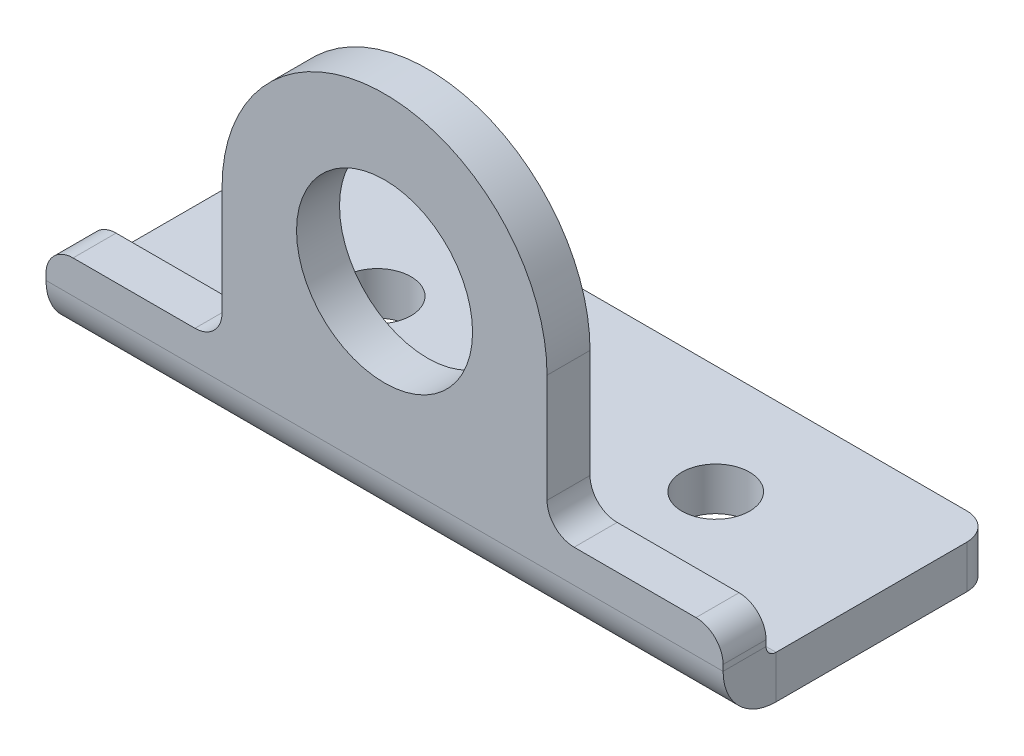
SolidWorks part; units mm, degrees
note: The reader was unsure of these and kept them because the rebuilt part matched: flange length of "Edge-Flange1".
ref_plane "Front Plane" through (0, 0, 0) normal (0, 0, 1) x (1, 0, 0)
ref_plane "Top Plane" through (0, 0, 0) normal (0, 1, 0) x (1, 0, 0)
ref_plane "Right Plane" through (0, 0, 0) normal (1, 0, 0) x (0, 0, -1)
sketch "Sketch1" plane through (0, 0, 0) normal (0, 0, 1) x (1, 0, 0)
  line L0 (-25, 0) -> (25, 0)
  line L1 (25, 0) -> (25, 1.175)
  line L2 (23, 3.175) -> (14, 3.175)
  line L3 (12, 5.175) -> (12, 13.175)
  line L4 (-12, 13.175) -> (-12, 5.175)
  line L5 (-14, 3.175) -> (-23, 3.175)
  line L6 (-25, 1.175) -> (-25, 0)
  arc A0 (12, 13.175) -> (-12, 13.175) centre (0, 13.175) ccw
  circle A1 centre (0, 13.175) radius 6.5
  arc A2 (25, 1.175) -> (23, 3.175) centre (23, 1.175) ccw
  arc A3 (-23, 3.175) -> (-25, 1.175) centre (-23, 1.175) ccw
  arc A4 (14, 3.175) -> (12, 5.175) centre (14, 5.175) cw
  arc A5 (-12, 5.175) -> (-14, 3.175) centre (-14, 5.175) cw
  point P4 (0, 0)
  point P16 (25, 3.175)
  point P21 (12, 3.175)
  dimension "D1" = 13
  dimension "D3" = 12
  dimension "D6" = 2
  dimension "D2" = 3.175
  dimension "D4" = 10
  dimension "D5" = 50
base flange "Base-Flange1" sketch "Sketch1" thickness 3.175 reverse thickness direction no parameters "D1"=0.7366
edge flange "Edge-Flange1" sketch "Sketch8" flange angle 90 flange length 20 flange position material outside bend radius 0.7366 thickness 3.175 relief rectangular parameters "D6"=10
sketch "Sketch8" plane through (0, 0, -3.175) normal (0, -1, 0) x (-1, 0, 0)
  line L0 (25, 0) -> (-25, 0) construction
  line L1 (25, 0) -> (-25, 0)
  line L2 (-25, 0) -> (-25, 16.825)
  line L3 (-25, 16.825) -> (25, 16.825)
  line L4 (25, 16.825) -> (25, 0)
bend "EdgeBend1" bend radius 0.7366 bend angle 90 parameters "D5"=1
fillet "Fillet2" radius 2 2 edges at (25, -1.5875, -20) (-25, -1.5875, -20)
hole_wizard "Ø5.0mm Dowel Hole1" positions "Sketch9" profile "Sketch10" hole size "Ø5.0" standard "ANSI Metric" end condition through all
sketch "Sketch9" plane through (0, 0, 0) normal (0, 1, 0) x (1, 0, 0)
  line L2 (-23, 20) -> (23, 20) construction
  line L3 (0, 3.9116) -> (0, 20) construction
  line L4 (25, 3.9116) -> (-25, 3.9116) construction
  line L6 (0, 11.9558) -> (25, 11.9558) construction
  line L7 (25, 18) -> (25, 3.9116) construction
  line L9 (0, 11.9558) -> (-25, 11.9558) construction
  line L10 (-25, 3.9116) -> (-25, 18) construction
  point P25 (12.5, 11.9558)
  point P34 (-12.5, 11.9558)
sketch "Sketch10" plane through (-12.5, 0, -11.9558) normal (1, 0, 0) x (0, 0, 1)
  line L0 (0, 0) -> (0, 3.175)
  line L1 (0, 3.175) -> (2.5, 3.175)
  line L2 (2.5, 3.175) -> (2.5, 0)
  line L5 (2.5, 0) -> (0, 0)
  line L11 (0, -6.35) -> (0, 107.95) construction
  dimension "Thru Hole Dia." = 5
  dimension "Thru Hole Depth" = 3.175
sketch "Bend-Lines1" [suppressed] plane through (0, 0, 0) normal (0, 1, 0) x (1, 0, 0)
sketch "Bounding-Box1" [suppressed] plane through (0, 0, 0) normal (0, 1, 0) x (1, 0, 0)
sheet metal parameters "Sheet-Metal1" thickness 3.175 parameters "D1"=0.7366
flat pattern "Flat-Pattern1" [suppressed]
sketch "Bend-Lines2" plane through (0, 0, 0) normal (0, 1, 0) x (1, 0, 0)
sketch3d "Bounding-Box2" [suppressed]
  line L0 (25, 11.9999, 0) -> (-25, 11.9999, 0) construction
  line L1 (25, -19.175, 0) -> (-25, -19.175, 0) construction
  line L2 (25, 11.9999, 0) -> (25, -19.175, 0) construction
  line L3 (-25, 11.9999, 0) -> (-25, -19.175, 0) construction
sheet metal parameters "Sheet-Metal2" thickness 3.175 parameters "D1"=0.7366
flat pattern "Flat-Pattern1"
sketch "Bend-Lines2" plane through (0, 0, 0) normal (0, 0, 1) x (1, 0, 0)
  line L0 (-25, -1.0887) -> (25, -1.0887) construction
  line L1 (-25, -1.0887) -> (25, -1.0887) construction
sketch3d "Bounding-Box2" [suppressed]
  line L0 (-48, 23.9999, 0) -> (2, 23.9999, 0) construction
  line L1 (-48, -20.1775, 0) -> (2, -20.1775, 0) construction
  line L2 (-48, 23.9999, 0) -> (-48, -20.1775, 0) construction
  line L3 (2, 23.9999, 0) -> (2, -20.1775, 0) construction
bend of the flat pattern "Flatten-<EdgeBend1>1"
sheet metal parameters "Sheet-Metal3" thickness 3.175 parameters "D1"=0.7366
flat pattern "Flat-Pattern1"
sketch "Bend-Lines2" plane through (0, 0, 0) normal (0, 0, 1) x (1, 0, 0)
  line L0 (-25, -1.0887) -> (25, -1.0887) construction
  line L1 (-25, -1.0887) -> (25, -1.0887) construction
sketch3d "Bounding-Box2" [suppressed]
  line L0 (-48, 23.9999, 0) -> (2, 23.9999, 0) construction
  line L1 (-48, -20.1775, 0) -> (2, -20.1775, 0) construction
  line L2 (-48, 23.9999, 0) -> (-48, -20.1775, 0) construction
  line L3 (2, 23.9999, 0) -> (2, -20.1775, 0) construction
bend of the flat pattern "Flatten-<EdgeBend1>1"
